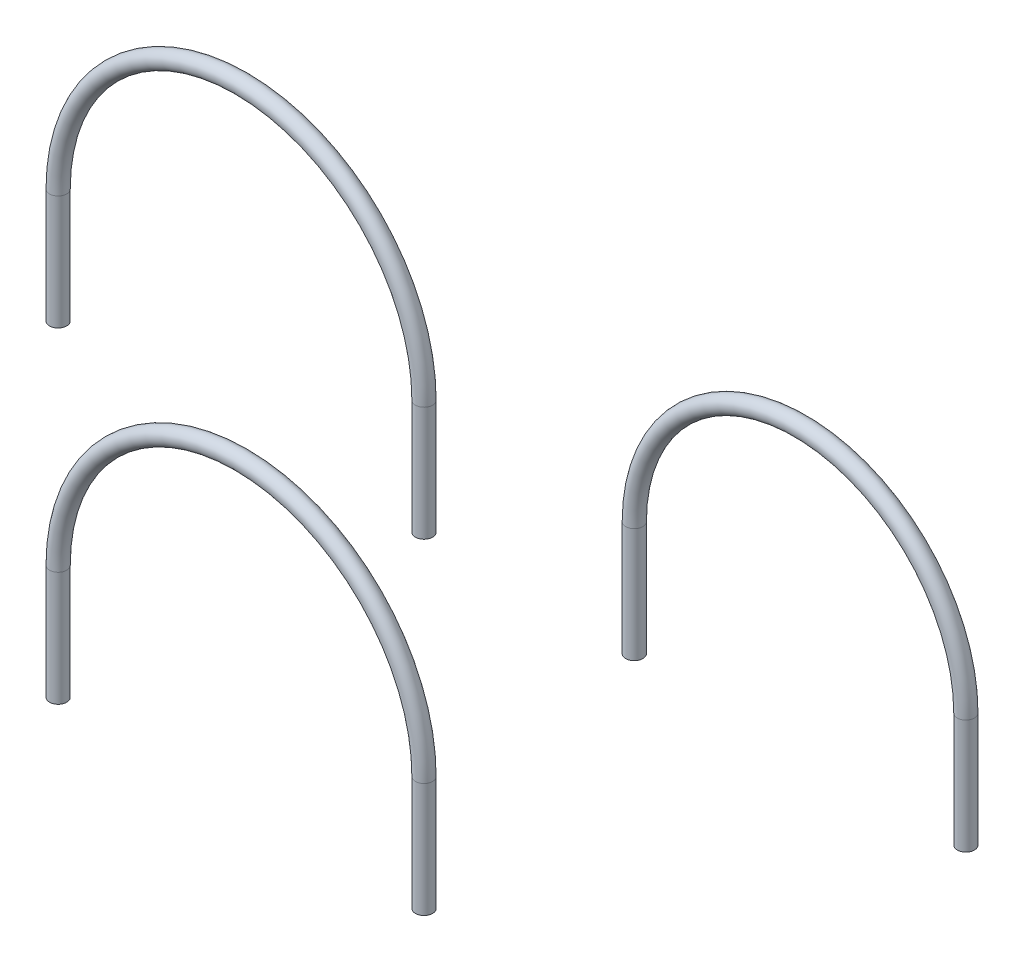
SolidWorks part; units mm, degrees
ref_plane "Plano frontal" through (0, 0, 0) normal (0, 0, 1) x (1, 0, 0)
ref_plane "Plano superior" through (0, 0, 0) normal (0, 1, 0) x (1, 0, 0)
ref_plane "Plano direito" through (0, 0, 0) normal (1, 0, 0) x (0, 0, -1)
sketch "Sketch1" plane through (0, 0, 0) normal (0, 0, 1) x (1, 0, 0)
  line L0 (-576.6684, 0) -> (-576.6684, -400)
  line L1 (703.3316, -400) -> (703.3316, 0)
  arc A0 (-576.6684, 0) -> (703.3316, 0) centre (63.3316, 0) cw
  dimension "D1" = 640
  dimension "D2" = 400
sweep "Sweep-Thin1" add path "Sketch1" circular profile diameter 60 parameters "D1"=3, "D3"=60
sketch "Sketch22" plane through (0, 0, 0) normal (0, 0, 1) x (1, 0, 0)
  line L0 (1438.967, 0) -> (1438.967, -400)
  line L1 (2598.967, 0) -> (2598.967, -400)
  arc A0 (1438.967, 0) -> (2598.967, 0) centre (2018.967, 0) cw
  dimension "D1" = 580
  dimension "D2" = 400
sweep "Sweep-Thin2" add path "Sketch22" circular profile diameter 60 parameters "D1"=3, "D3"=60
pattern_linear "LPattern1" count 2 spacing 1140 along (0, -1, 0) of bodies 101
